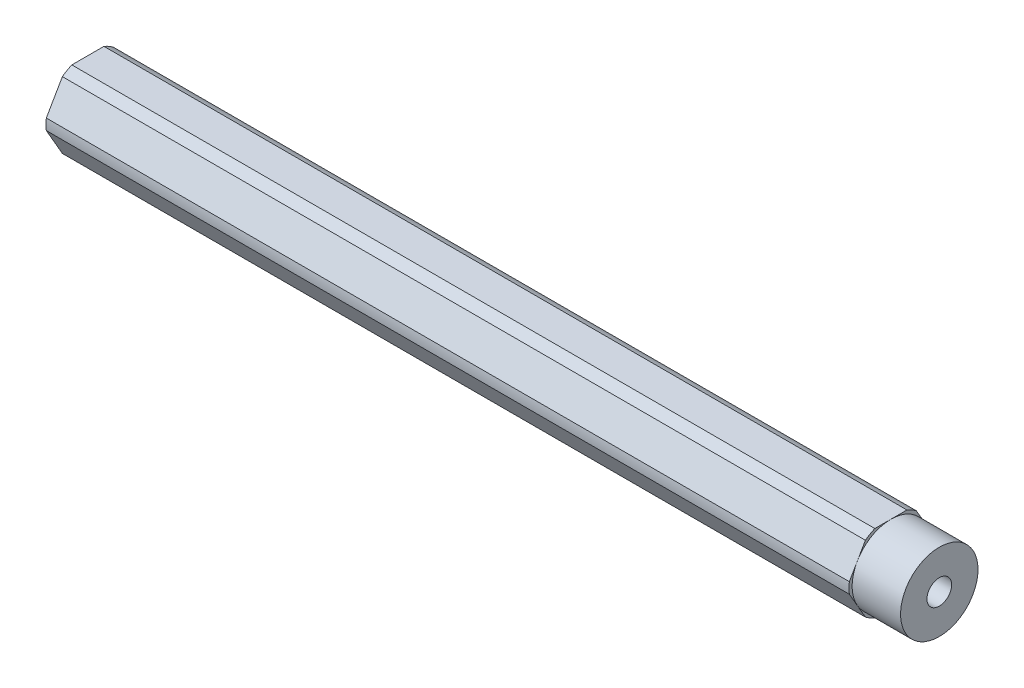
SolidWorks part; units mm, degrees
material "7075-T6 (SN)"
ref_plane "Front Plane" through (0, 0, 0) normal (0, 0, 1) x (1, 0, 0)
ref_plane "Top Plane" through (0, 0, 0) normal (0, 1, 0) x (1, 0, 0)
ref_plane "Right Plane" through (0, 0, 0) normal (1, 0, 0) x (0, 0, -1)
sketch "Sketch1" plane through (0, 0, 0) normal (1, 0, 0) x (0, 0, -1)
  line L1 (3.6662, 6.35) -> (-3.6662, 6.35)
  line L2 (-3.6662, 6.35) -> (-7.3323, 0)
  line L3 (-7.3323, 0) -> (-3.6662, -6.35)
  line L4 (-3.6662, -6.35) -> (3.6662, -6.35)
  line L5 (3.6662, -6.35) -> (7.3323, 0)
  line L6 (7.3323, 0) -> (3.6662, 6.35)
  circle A0 centre (0, 0) radius 6.875
  circle A1 centre (0, 0) radius 2.0193
  circle A2 centre (0, 0) radius 6.35 construction
  dimension "D1" = 12.7
  dimension "D2" = 13.75
  dimension "D3" = 4.0386
extrude "Boss-Extrude1" add sketch "Sketch1" along normal mid plane 139.6492 contours L6 A0 L1 L2 L3 L4 L5 A1 region at (0, 5.7918, -3.3439)
hole_wizard "#10-32 Tapped Hole1" positions "3DSketch1" profile "Sketch2" tap size "#10-32" standard "ANSI Inch"
sketch3d "3DSketch1"
  circle A0 centre (-69.8246, 0, 0) radius 2.0193 construction
  circle A1 centre (69.8246, 0, 0) radius 2.0193 construction
  point P0 (69.8246, 0, 0)
  point P2 (-69.8246, 0, 0)
  point P7 (-67.8053, 0, 0)
  point P10 (71.8439, 0, 0)
sketch "Sketch2" plane through (69.8246, 0, 0) normal (0, 1, 0) x (0, 0, -1)
  line L0 (0, 0) -> (0, 17.5608)
  line L1 (0, 17.5608) -> (2.0193, 16.3474)
  line L2 (2.0193, 16.3474) -> (2.0193, 0)
  line L5 (2.0193, 0) -> (0, 0)
  line L10 (0, 17.5608) -> (-2.0193, 16.3474) construction
  line L11 (0, -6.35) -> (0, 107.95) construction
  dimension "Tap Drill Dia." = 4.0386
  dimension "Tap Drill Depth" = 16.3474
  dimension "Drill Angle" = 118
cosmetic thread "Hole Thread1" parameters "D1"=13.97, "D2"=4.826
cosmetic thread "Hole Thread2" parameters "D1"=13.97, "D2"=4.826
sketch "Sketch3" plane through (69.8246, 0, 0) normal (1, 0, 0) x (0, 0, -1)
  circle A0 centre (0, 0) radius 6.35
  dimension "D1" = 12.7
extrude "Cut-Extrude-Thin1" cut sketch "Sketch3" against normal blind 7.9375 thin thin type one direction wall 2.54
equation "\"D2@Sketch1\"=13.75mm"
